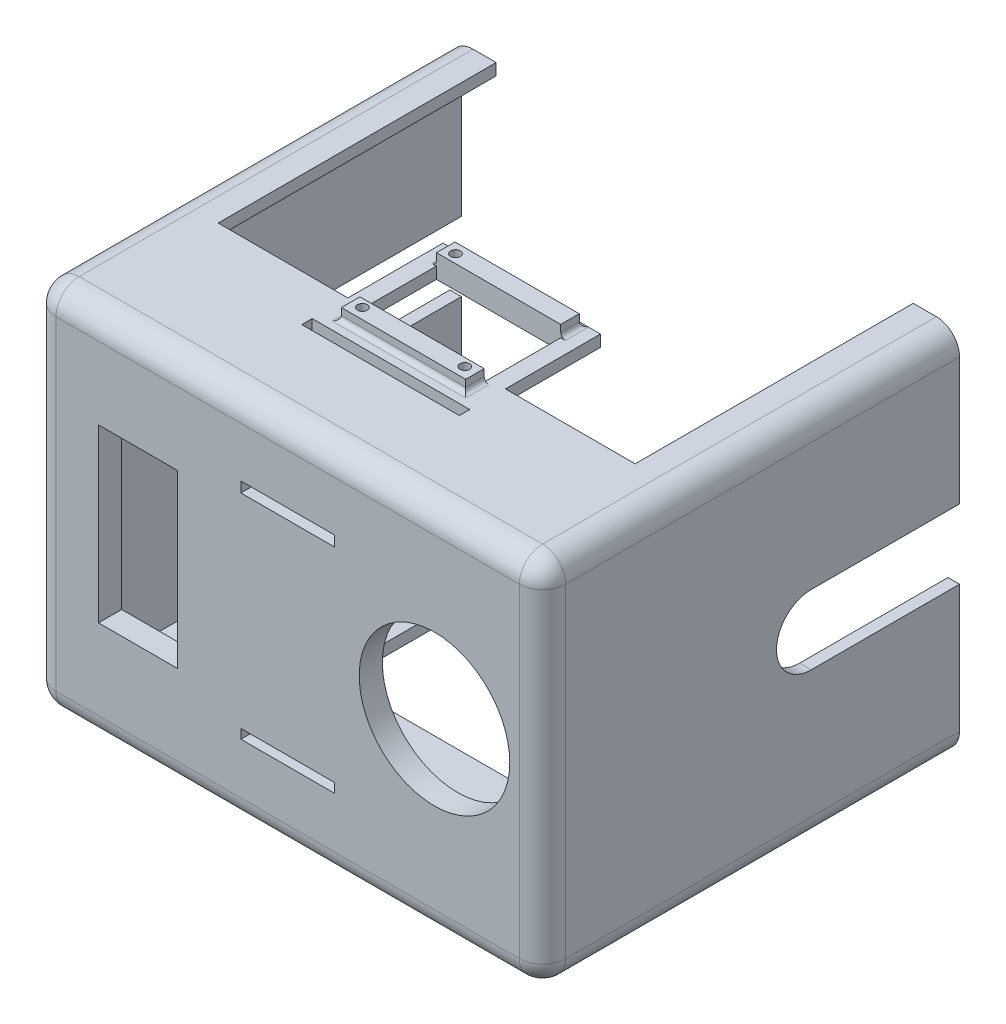
SolidWorks part; units mm, degrees
ref_plane "Plan de face" through (0, 0, 0) normal (0, 0, 1) x (1, 0, 0)
ref_plane "Plan de dessus" through (0, 0, 0) normal (0, 1, 0) x (1, 0, 0)
ref_plane "Plan de droite" through (0, 0, 0) normal (1, 0, 0) x (0, 0, -1)
sketch "Esquisse1" plane through (0, 0, 0) normal (0, 1, 0) x (1, 0, 0)
  line L1 (-48.5287, 46.8615) -> (61.4713, 46.8615)
  line L2 (-48.5287, 46.8615) -> (-48.5287, -53.1385)
  line L3 (-48.5287, -53.1385) -> (61.4713, -53.1385)
  line L4 (61.4713, 46.8615) -> (61.4713, -53.1385)
  point P10 (-45.5809, 46.8615)
  point P11 (-10.7604, 46.8615)
  point P12 (-6.0287, 46.8615)
  point P13 (13.9713, 46.8615)
  point P14 (27.7429, 46.8615)
  point P15 (44.6509, 46.8615)
  dimension "D1" = 100
  dimension "D2" = 110
extrude "Boss.-Extru.1" add sketch "Esquisse1" along normal blind 80
sketch "Esquisse3" plane through (0, 0, -46.8615) normal (0, 0, -1) x (-1, 0, 0)
  line L0 (-61.4713, 80) -> (-61.4713, 0) construction
  line L1 (-58.9713, 77.5) -> (46.0287, 77.5)
  line L2 (-58.9713, 77.5) -> (-58.9713, 2.5)
  line L3 (-58.9713, 2.5) -> (46.0287, 2.5)
  line L4 (46.0287, 77.5) -> (46.0287, 2.5)
  line L5 (-61.4713, 0) -> (48.5287, 0) construction
  dimension "D1" = 75
  dimension "D2" = 105
  dimension "D3" = 2.5
  dimension "D4" = 2.5
extrude "Enlèv. mat.-Extru.1" cut sketch "Esquisse3" against normal blind 95
sketch "Esquisse4" plane through (0, 0, 53.1385) normal (0, 0, 1) x (1, 0, 0)
  line L0 (-34.3516, 59.3625) -> (-17.3516, 59.3625)
  line L1 (-34.3516, 59.3625) -> (-34.3516, 22.3625)
  line L2 (-34.3516, 22.3625) -> (-17.3516, 22.3625)
  line L3 (-17.3516, 59.3625) -> (-17.3516, 22.3625)
  line L4 (-3.6381, 62.0051) -> (16.5807, 62.0051)
  line L5 (-3.6381, 62.0051) -> (-3.6381, 64.2451)
  line L6 (-3.6381, 64.2451) -> (16.5807, 64.2451)
  line L7 (16.5807, 62.0051) -> (16.5807, 64.2451)
  line L8 (-3.6393, 15.9751) -> (16.5807, 15.9751)
  line L9 (-3.6393, 15.9751) -> (-3.6393, 17.9949)
  line L10 (-3.6393, 17.9949) -> (16.5807, 17.9949)
  line L11 (16.5807, 15.9751) -> (16.5807, 17.9949)
  line L12 (-48.5287, 0) -> (61.4713, 0) construction
  line L13 (6.4713, 62.0051) -> (6.4713, 17.9949) construction
  line L15 (-48.5287, 80) -> (-48.5287, 0) construction
  line L16 (-48.5287, 40) -> (61.4713, 40) construction
  line L17 (61.4713, 80) -> (61.4713, 0) construction
  circle A0 centre (38.1549, 40.6366) radius 16.25
  point P18 (6.4713, 0)
  dimension "D1" = 32.5
  dimension "D2" = 44.0102
  dimension "D3" = 2.24
extrude "Enlèv. mat.-Extru.2" cut sketch "Esquisse4" against normal through all
fillet "Congé2" radius 5 8 edges at (61.4713, 40, 53.1385) (61.4713, 80, 3.1385) (61.4713, 0, 3.1385) (6.4713, 80, 53.1385) (-48.5287, 80, 3.1385) (-48.5287, 40, 53.1385) (-48.5287, 0, 3.1385) (6.4713, 0, 53.1385)
sketch "Esquisse5" plane through (0, 0, 0) normal (0, -1, 0) x (1, 0, 0)
  line L0 (6.4713, -46.8615) -> (32.4713, -46.8615)
  line L1 (56.4713, -46.8615) -> (-43.5287, -46.8615) construction
  line L2 (6.4713, -46.8615) -> (-19.5287, -46.8615)
  line L3 (-19.5287, -46.8615) -> (-19.5287, 18.1385)
  line L4 (-19.5287, 18.1385) -> (32.4713, 18.1385)
  line L5 (32.4713, 18.1385) -> (32.4713, -46.8615)
  dimension "D1" = 26
  dimension "D2" = 26
  dimension "D3" = 65
extrude "Enlèv. mat.-Extru.3" cut sketch "Esquisse5" against normal blind 25
sketch "Esquisse6" plane through (-48.5287, 0, 0) normal (-1, 0, 0) x (0, 0, 1)
  line L0 (-46.8615, 40) -> (-4.8615, 40) construction
  line L1 (-46.8615, 75) -> (-46.8615, 5) construction
  line L2 (-4.8615, 47.5) -> (-46.8615, 47.5)
  line L3 (-4.8615, 32.5) -> (-46.8615, 32.5)
  line L4 (-46.8615, 47.5) -> (-46.8615, 32.5)
  arc A0 (-4.8615, 32.5) -> (-4.8615, 47.5) centre (-4.8615, 40) ccw
  dimension "D2" = 15
  dimension "D1" = 42
extrude "Enlèv. mat.-Extru.4" cut sketch "Esquisse6" against normal through all
sketch "Esquisse7" plane through (0, 0, 0) normal (0, -1, 0) x (1, 0, 0)
  line L1 (-48.5287, -46.8615) -> (61.4713, -46.8615)
  line L2 (-48.5287, -46.8615) -> (-48.5287, -36.8615)
  line L3 (-48.5287, -36.8615) -> (61.4713, -36.8615)
  line L4 (61.4713, -46.8615) -> (61.4713, -36.8615)
  dimension "D1" = 10
extrude "Enlèv. mat.-Extru.5" cut sketch "Esquisse7" against normal through all
sketch "Esquisse8" plane through (0, 80, 0) normal (0, 1, 0) x (1, 0, 0)
  line L0 (6.4713, -48.1385) -> (6.4713, -24.1385) construction
  line L32 (17.4061, -25.8459) -> (16.3561, -25.8459) construction
  line L37 (-6.9403, -28.1385) -> (19.8828, -28.1385)
  line L38 (-6.9403, -28.1385) -> (-6.9403, -24.1385)
  line L39 (-6.9403, -3.6192) -> (19.8828, -3.6192)
  line L40 (19.8828, -28.1385) -> (19.8828, -24.1385)
  line L41 (2.4066, -3.6192) -> (2.4066, -7.6192) construction
  line L42 (-43.5287, -48.1385) -> (56.4713, -48.1385) construction
  line L43 (56.4713, 36.8615) -> (-43.5287, 36.8615) construction
  line L44 (2.4066, -7.6192) -> (19.8828, -7.6192)
  line L45 (2.4066, -7.6192) -> (-6.9403, -7.6192)
  line L46 (-3.6439, -25.8459) -> (-4.6939, -25.8459) construction
  line L47 (2.4066, -28.1385) -> (2.4066, -24.1385) construction
  line L48 (2.4066, -24.1385) -> (19.8828, -24.1385)
  line L49 (2.4066, -24.1385) -> (-6.9403, -24.1385)
  line L50 (-6.9403, -7.6192) -> (-6.9403, -3.6192)
  line L51 (6.4713, -7.6192) -> (6.4713, 36.8615) construction
  line L52 (19.8828, -7.6192) -> (19.8828, -3.6192)
  circle A5 centre (17.4061, -25.8459) radius 1.05
  circle A6 centre (-4.6939, -25.8459) radius 1.05
  circle A7 centre (-4.6939, -5.7459) radius 1.05
  point P7 (6.4713, -28.1385)
  dimension "D2" = 2.1
  dimension "D3" = 2.1
  dimension "D4" = 2.1
  dimension "D1" = 20
extrude "Boss.-Extru.4" add sketch "Esquisse8" along normal blind 2.5
sketch "Esquisse12" plane through (0, 80, 0) normal (0, 1, 0) x (1, 0, 0)
  line L1 (-6.9403, -7.6192) -> (19.8828, -7.6192)
  line L2 (-6.9403, -7.6192) -> (-6.9403, -24.1385)
  line L3 (-6.9403, -24.1385) -> (19.8828, -24.1385)
  line L4 (19.8828, -7.6192) -> (19.8828, -24.1385)
extrude "Enlèv. mat.-Extru.8" cut sketch "Esquisse12" against normal blind 2.5
fillet "Congé3" radius 1 6 edges at (-6.9403, 80, 5.6192) (19.8828, 80, 5.6192) (6.4713, 80, 3.6192) (19.8828, 80, 26.1385) (6.4713, 80, 28.1385) (-6.9403, 80, 26.1385)
sketch "Esquisse13" plane through (0, 80, 0) normal (0, 1, 0) x (1, 0, 0)
  line L0 (-43.5287, 36.8615) -> (-43.5287, -48.1385) construction
  line L1 (-38.5287, 36.8615) -> (51.4713, 36.8615)
  line L2 (-38.5287, 36.8615) -> (-38.5287, -23.1385)
  line L3 (-10.5287, -2.6192) -> (23.4713, -2.6192)
  line L5 (56.4713, 36.8615) -> (-43.5287, 36.8615) construction
  line L6 (-7.9403, -2.6192) -> (20.8828, -2.6192) construction
  line L7 (51.4713, 36.8615) -> (51.4713, -23.1385)
  line L10 (-38.5287, -23.1385) -> (-10.5287, -23.1385)
  line L11 (-10.5287, -2.6192) -> (-10.5287, -23.1385)
  line L14 (51.4713, -23.1385) -> (23.4713, -23.1385)
  line L15 (23.4713, -2.6192) -> (23.4713, -23.1385)
  line L17 (-10.5287, -33.0959) -> (23.4713, -33.0959)
  line L18 (-10.5287, -33.0959) -> (-10.5287, -30.8459)
  line L19 (-10.5287, -30.8459) -> (23.4713, -30.8459)
  line L20 (23.4713, -33.0959) -> (23.4713, -30.8459)
  circle A0 centre (-4.6939, -25.8459) radius 1.05 construction
  dimension "D1" = 90
  dimension "D2" = 5
  dimension "D3" = 0
  dimension "D4" = 0
  dimension "D5" = 60
  dimension "D6" = 34
  dimension "D7" = 5
  dimension "D8" = 2.25
extrude "Enlèv. mat.-Extru.9" cut sketch "Esquisse13" against normal blind 10
